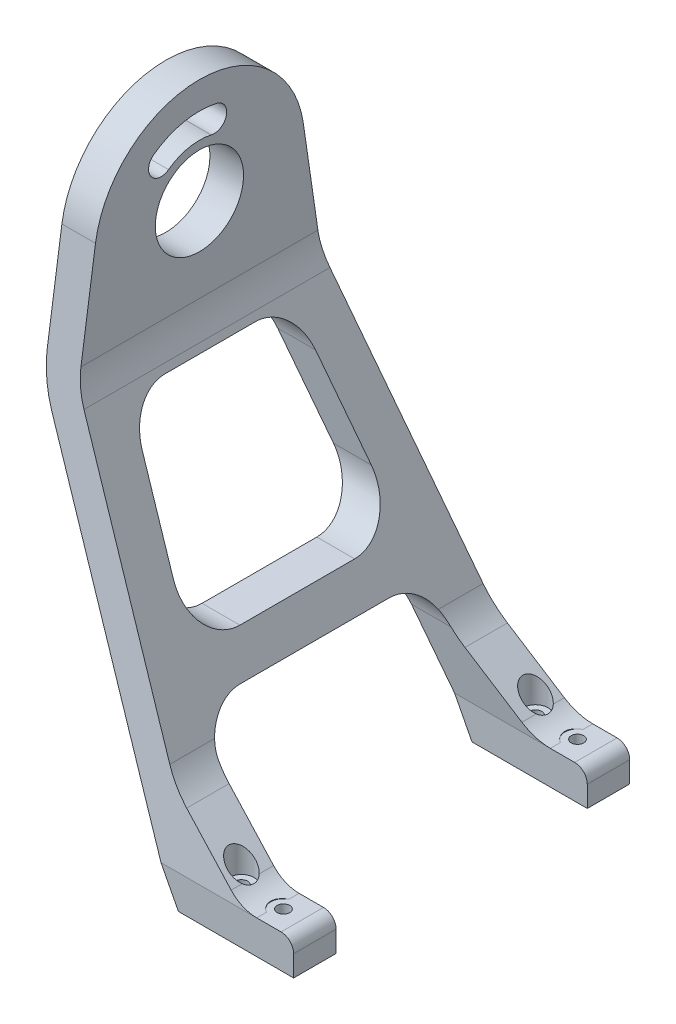
SolidWorks part; units mm, degrees
material "6061 合金"
ref_plane "前视基准面" through (0, 0, 0) normal (0, 0, 1) x (1, 0, 0)
ref_plane "上视基准面" through (0, 0, 0) normal (0, 1, 0) x (1, 0, 0)
ref_plane "右视基准面" through (0, 0, 0) normal (1, 0, 0) x (0, 0, -1)
sketch "草图1" plane through (0, 0, 0) normal (0, 0, 1) x (1, 0, 0)
  line L0 (0, 50) -> (0, 4.8715)
  line L1 (2.2402, -4.3258) -> (41.43, -80)
  line L2 (41.43, -80) -> (66.43, -80)
  arc A0 (2.2402, -4.3258) -> (0, 4.8715) centre (20, 4.8715) cw
  point P7 (0, 0)
  dimension "D5" = 20
  dimension "D1" = 80
  dimension "D2" = 41.43
  dimension "D3" = 50
  dimension "D4" = 25
extrude "拉伸-薄壁1" add sketch "草图1" along normal blind 80 thin thin type mid plane wall 8
sketch "草图9" plane through (0, 0, 0) normal (0, 0, -1) x (-1, 0, 0)
  line L0 (-53.9969, -76) -> (-36.0752, -60.9619)
  line L1 (-43.8631, -76) -> (-66.43, -76) construction
  line L2 (-5.7922, -2.4864) -> (-43.8631, -76) construction
  line L3 (-36.0752, -60.9619) -> (-43.8631, -76)
  line L4 (-43.8631, -76) -> (-53.9969, -76)
  dimension "D1" = 40
  dimension "D2" = 15
extrude "凸台-拉伸1" add sketch "草图9" against normal through all
sketch "草图2" plane through (-4, 0, 0) normal (-1, 0, 0) x (0, 0, 1)
  line L0 (80, 50) -> (0, 50) construction
  line L1 (15.2619, 28.6092) -> (0, -76)
  line L2 (0, -6.1653) -> (0, -84) construction
  line L3 (40, 85.5078) -> (40, -146.0129) construction
  line L4 (80, -84) -> (0, -84) construction
  line L5 (64.7381, 28.6092) -> (80, -76)
  line L9 (0, 50) -> (0, -76)
  line L10 (80, -76) -> (80, 50)
  line L11 (80, 50) -> (0, 50)
  arc A0 (15.2619, 28.6092) -> (64.7381, 28.6092) centre (40, 25) cw
  point P6 (40, 50)
  dimension "D1" = 25
  dimension "D2" = 8
extrude "切除-拉伸1" cut sketch "草图2" against normal through all
fillet "圆角3" radius 10 1 edges at (53.9969, -76, 40)
sketch "草图3" plane through (0, -84, 0) normal (0, -1, 0) x (1, 0, 0)
  line L0 (-21.9643, 40) -> (81.8416, 40) construction
  line L1 (66.43, 80) -> (66.43, 0) construction
  line L2 (38.9969, 80) -> (38.9969, 0) construction
  line L3 (38.9969, 80) -> (66.43, 80) construction
  circle A0 centre (48.9969, 75) radius 1.5
  circle A1 centre (58.9969, 75) radius 1.5
  circle A2 centre (58.9969, 5) radius 1.5
  circle A3 centre (48.9969, 5) radius 1.5
  point P9 (66.43, 40)
  dimension "D4" = 3
  dimension "D1" = 10
  dimension "D2" = 10
  dimension "D3" = 5
extrude "切除-拉伸2" cut sketch "草图3" against normal through all
sketch "草图5" plane through (-4, 0, 0) normal (-1, 0, 0) x (0, 0, 1)
  line L0 (10.1059, -76) -> (10.1059, -84)
  line L1 (0, -76) -> (10.1885, -6.1653) construction
  line L2 (10.1059, -76) -> (13.6073, -52)
  line L3 (20.6103, -4) -> (59.3897, -4)
  line L4 (59.3897, -4) -> (65.2255, -44)
  line L5 (14.7745, -44) -> (65.2255, -44)
  line L6 (80, -84) -> (0, -84) construction
  line L7 (40, 64.2186) -> (40, -117.6272) construction
  line L8 (10.1059, -84) -> (69.8941, -84)
  line L9 (69.8941, -84) -> (69.8941, -76)
  line L10 (13.6073, -52) -> (66.3927, -52)
  line L11 (66.3927, -52) -> (69.8941, -76)
  line L12 (14.7745, -44) -> (20.6103, -4)
  dimension "D1" = 10
  dimension "D2" = 8
  dimension "D3" = 80
  dimension "D4" = 8
  dimension "D5" = 40
sketch "草图6" plane through (4, 0, 0) normal (1, 0, 0) x (0, 0, -1)
  line L0 (-49.1107, 37.5398) -> (-40, 25) construction
  line L1 (-40, 25) -> (-36.5133, 40.1027) construction
  line L2 (-40, 67.7902) -> (-40, -22.8803) construction
  circle A0 centre (-40, 25) radius 10.5
  arc A1 (-49.1107, 37.5398) -> (-36.5133, 40.1027) centre (-40, 25) cw construction
  arc A2 (-35.8384, 43.0258) -> (-50.874, 39.9668) centre (-40, 25) ccw
  arc A3 (-37.1881, 37.1796) -> (-47.3473, 35.1127) centre (-40, 25) ccw
  arc A4 (-37.1881, 37.1796) -> (-35.8384, 43.0258) centre (-36.5133, 40.1027) ccw
  arc A5 (-50.874, 39.9668) -> (-47.3473, 35.1127) centre (-49.1107, 37.5398) ccw
  point P5 (-43.0902, 40.1888)
  point P11 (-40, 25)
  dimension "D1" = 21
  dimension "D3" = 3
  dimension "D2" = 15.5
  dimension "D4" = 36
  dimension "D5" = 13
extrude "切除-拉伸5" cut sketch "草图6" against normal through all
ref_plane "基准面1" through (0, 0, 40) normal (0, 0, 1) x (1, 0, 0)
sketch "草图8" plane through (0, 0, 40) normal (0, 0, 1) x (1, 0, 0)
  line L0 (88.9969, 55.6878) -> (88.9969, -81.9949) construction
  dimension "D1" = 50
extrude "切除-拉伸6" cut sketch "草图5" against normal through all
fillet "圆角2" radius 10 6 edges at (2.138, -4, 59.3897) (26.9295, -52, 66.3927) (26.9295, -52, 13.6073) (22.7865, -44, 65.2255) (22.7865, -44, 14.7745) (2.138, -4, 20.6103)
ref_plane "基准面2" through (0, -66, 0) normal (0, 1, 0) x (1, 0, 0)
sketch "草图10" plane through (0, -66, 0) normal (0, 1, 0) x (1, 0, 0)
  circle A0 centre (48.9969, -5) radius 3
  circle A1 centre (58.9969, -5) radius 3
  circle A2 centre (58.9969, -75) radius 3
  circle A3 centre (48.9969, -75) radius 3
  dimension "D1" = 6
  dimension "D2" = 6
  dimension "D3" = 6
  dimension "D4" = 6
extrude "切除-拉伸7" cut sketch "草图10" against normal blind 10
fillet "圆角4" radius 3 2 edges at (66.43, -76, 5.0529) (66.43, -76, 74.9471)
fillet "圆角5" radius 20 2 edges at (36.0752, -60.9619, 7.2469) (36.0752, -60.9619, 72.7531)
